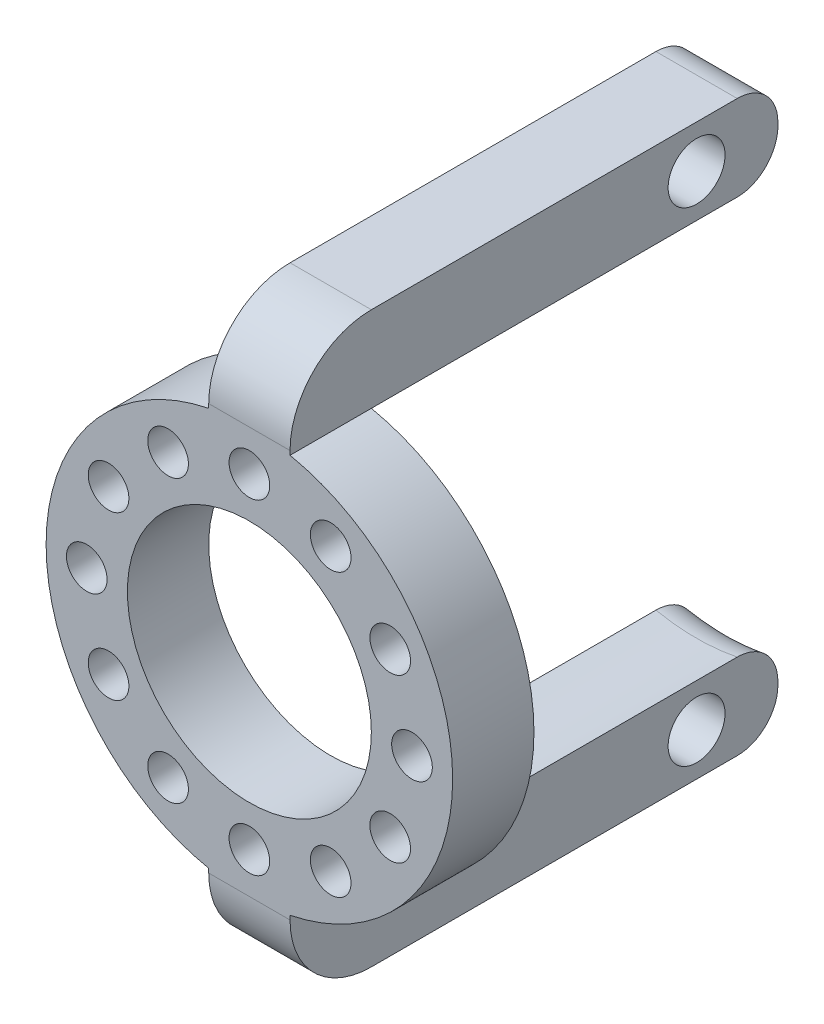
SolidWorks part; units mm, degrees
ref_plane "前视基准面" through (0, 0, 0) normal (0, 0, 1) x (1, 0, 0)
ref_plane "上视基准面" through (0, 0, 0) normal (0, 1, 0) x (1, 0, 0)
ref_plane "右视基准面" through (0, 0, 0) normal (1, 0, 0) x (0, 0, -1)
other "Configuration Table"
sketch "Sketch1" plane through (0, 0, 0) normal (0, 0, 1) x (1, 0, 0)
  circle A0 centre (0, 0) radius 12.5
  circle A1 centre (0, 0) radius 7.5
  dimension "D1" = 25
  dimension "D2" = 15
extrude "Boss-Extrude1" add sketch "Sketch1" along normal blind 5
sketch "Sketch4" plane through (0, 0, 5) normal (0, 0, 1) x (1, 0, 0)
  line L1 (-2.5, -17.5) -> (2.5, -17.5)
  line L2 (-2.5, -17.5) -> (-2.5, 17.5)
  line L3 (-2.5, 17.5) -> (2.5, 17.5)
  line L4 (2.5, -17.5) -> (2.5, 17.5)
  line L5 (-2.5, -17.5) -> (2.5, 17.5) construction
  line L6 (-2.5, 17.5) -> (2.5, -17.5) construction
  circle A0 centre (0, 0) radius 7.5
  circle A1 centre (0, 0) radius 12.5
  point P0 (0, 0)
  circle M15 centre (0, 0) radius 12.5
  dimension "D3" = 15
  dimension "D4" = 25
  dimension "D1" = 5
  dimension "D2" = 35
sketch "Sketch3" plane through (0, 0, 5) normal (0, 0, 1) x (1, 0, 0)
  circle A0 centre (0, 0) radius 10 construction
  circle A1 centre (0, 10) radius 1.25
  circle A2 centre (0, 0) radius 10 construction
  circle A3 centre (5, 8.6603) radius 1.25
  circle A4 centre (0, 0) radius 10 construction
  circle A5 centre (8.6603, 5) radius 1.25
  circle A6 centre (0, 0) radius 10 construction
  circle A7 centre (10, 0) radius 1.25
  circle A8 centre (0, 0) radius 10 construction
  circle A9 centre (8.6603, -5) radius 1.25
  circle A10 centre (0, 0) radius 10 construction
  circle A11 centre (5, -8.6603) radius 1.25
  circle A12 centre (0, 0) radius 10 construction
  circle A13 centre (0, -10) radius 1.25
  circle A14 centre (0, 0) radius 10 construction
  circle A15 centre (-5, -8.6603) radius 1.25
  circle A16 centre (0, 0) radius 10 construction
  circle A17 centre (-8.6603, -5) radius 1.25
  circle A18 centre (0, 0) radius 10 construction
  circle A19 centre (-10, 0) radius 1.25
  circle A20 centre (0, 0) radius 10 construction
  circle A21 centre (-8.6603, 5) radius 1.25
  circle A22 centre (0, 0) radius 10 construction
  circle A23 centre (-5, 8.6603) radius 1.25
  point P40 (0, 0)
  dimension "D1" = 20
  dimension "D2" = 2.5
  dimension "D3" = 12
extrude "Cut-Extrude1" cut sketch "Sketch3" against normal blind 5
extrude "Boss-Extrude2" add sketch "Sketch4" against normal blind 30 contours L4 L3 L2 M15 | L1 L4 L2 M15 region at (0, -14.9575, 5) region at (0, 14.9575, 5)
sketch "Sketch6" plane through (2.5, 0, 0) normal (1, 0, 0) x (0, 0, -1)
  line L0 (25, 14.8737) -> (20, 14.8737) construction
  line L1 (25, 12.2474) -> (25, 17.5) construction
  line L2 (0, 0) -> (20.6841, 0) construction
  circle A0 centre (20, 14.8737) radius 1.75
  circle A1 centre (20, -14.8737) radius 1.75
  dimension "D1" = 3.5
  dimension "D2" = 5
extrude "Cut-Extrude2" cut sketch "Sketch6" against normal through all
fillet "Fillet1" radius 5 2 edges at (0, 17.5, 5) (0, -17.5, 5)
fillet "Fillet2" radius 2.5 4 edges at (0, 17.5, -25) (0, 12.5, -25) (0, -12.5, -25) (0, -17.5, -25)
